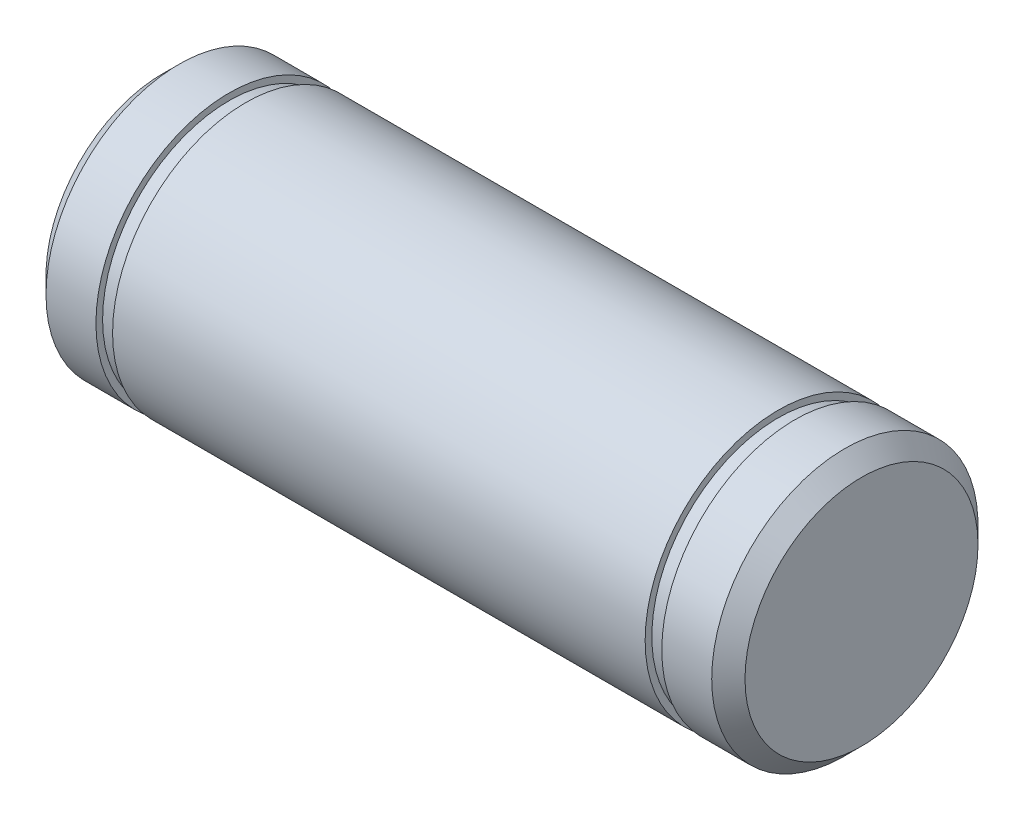
SolidWorks part; units mm, degrees
ref_plane "Front" through (0, 0, 0) normal (0, 0, 1) x (1, 0, 0)
ref_plane "Top" through (0, 0, 0) normal (0, 1, 0) x (1, 0, 0)
ref_plane "Right" through (0, 0, 0) normal (1, 0, 0) x (0, 0, -1)
sketch "Sketch1" plane through (0, 0, 0) normal (1, 0, 0) x (0, 0, -1)
  circle A0 centre (0, 0) radius 2
  dimension "D1" = 4
extrude "Boss-Extrude1" add sketch "Sketch1" along normal blind 10.5
sketch "Sketch2" plane through (10.5, 0, 0) normal (1, 0, 0) x (0, 0, -1)
  circle A0 centre (0, 0) radius 1.9
  circle A1 centre (0, 0) radius 2.4981
  dimension "D1" = 3.8
extrude "Cut-Extrude2" cut sketch "Sketch2" against normal blind 0.25 from offset 1 offset against normal yes
sketch "Sketch3" plane through (0, 0, 0) normal (-1, 0, 0) x (0, 0, 1)
  circle A0 centre (0, 0) radius 1.9
  circle A1 centre (0, 0) radius 2.5
extrude "Cut-Extrude3" cut sketch "Sketch3" against normal blind 0.25 from offset 1 offset against normal yes
chamfer "Chamfer1" distance 0.25 angle 45 2 edges at (0, 0, -2) (10.5, 0, -2)
